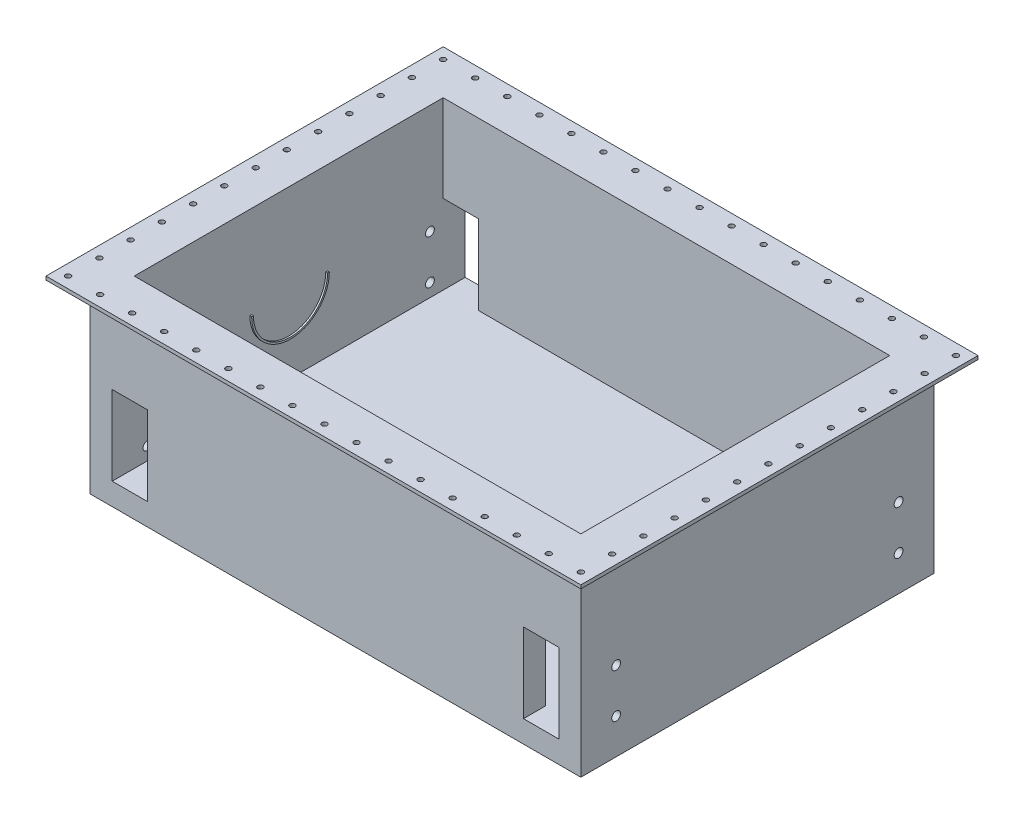
SolidWorks part; units mm, degrees
ref_plane "Front Plane" through (0, 0, 0) normal (0, 0, 1) x (1, 0, 0)
ref_plane "Top Plane" through (0, 0, 0) normal (0, 1, 0) x (1, 0, 0)
ref_plane "Right Plane" through (0, 0, 0) normal (1, 0, 0) x (0, 0, -1)
sketch "Sketch2" plane through (0, 0, 0) normal (0, 1, 0) x (1, 0, 0)
  line L0 (0, 437.5) -> (0, -437.5) construction
  line L1 (-632.5, 437.5) -> (632.5, 437.5)
  line L2 (-632.5, 437.5) -> (-632.5, -437.5)
  line L3 (-632.5, -437.5) -> (632.5, -437.5)
  line L4 (632.5, 437.5) -> (632.5, -437.5)
  line L5 (-632.5, 0) -> (632.5, 0) construction
  line L6 (-695, 48.7342) -> (-632.5, 48.7342) construction
  line L7 (-695, 500) -> (695, 500)
  line L8 (-695, 500) -> (-695, -500)
  line L9 (-695, -500) -> (695, -500)
  line L10 (695, 500) -> (695, -500)
  line L11 (632.5, 75.1796) -> (695, 75.1796) construction
  line L12 (-4.9015, 500) -> (-4.9015, 437.5) construction
  line L13 (-4.9015, -437.5) -> (-4.9015, -500) construction
  dimension "D1" = 62.5
  dimension "D2" = 1000
  dimension "D3" = 1390
extrude "Boss-Extrude1" add sketch "Sketch2" against normal blind 534.5
sketch "Sketch3" plane through (0, -534.5, 0) normal (0, -1, 0) x (1, 0, 0)
  line L0 (-695, 500) -> (-695, -500)
  line L3 (-695, 500) -> (695, 500)
  line L4 (695, -500) -> (695, 500)
  line L5 (-695, -500) -> (695, -500)
  line L6 (695, 500) -> (695, -500) construction
  line L7 (-695, 500) -> (695, 500) construction
  line L8 (-695, -500) -> (-695, 500) construction
  line L9 (695, -500) -> (-695, -500) construction
  point P0 (712.3016, -525.5001)
extrude "Boss-Extrude2" add sketch "Sketch3" against normal blind 62.5
sketch "Sketch4" plane through (695, 0, 0) normal (1, 0, 0) x (0, 0, -1)
  line L1 (0, 0) -> (0, -580.2055) construction
  line L2 (-105, -261) -> (-110, -261)
  line L3 (105, -261) -> (110, -261)
  arc A0 (-105, -261) -> (105, -261) centre (0, -261) ccw
  arc A1 (-110, -261) -> (110, -261) centre (0, -261) ccw
  dimension "D2" = 210
  dimension "D3" = 220
  dimension "D1" = 261
extrude "MMRTG Holder" add sketch "Sketch4" against normal blind 5 from offset 62.5 offset against normal yes
mirror "Mirror1" about plane through (0, 0, 0) normal (1, 0, 0) of "MMRTG Holder"
sketch "Sketch5" plane through (695, 0, 0) normal (1, 0, 0) x (0, 0, -1)
  line L0 (0, 70.8163) -> (0, -598.8061) construction
  line L1 (-500, -534.5) -> (500, -534.5) construction
  line L2 (-500, -534.5) -> (-500, 0) construction
  line L3 (-400, 39.1953) -> (-400, -618.3368) construction
  circle A0 centre (-400, -309.5) radius 12.5
  circle A1 centre (-400, -434.5) radius 12.5
  circle A2 centre (400, -434.5) radius 12.5
  circle A3 centre (400, -309.5) radius 12.5
  point P13 (-400, -434.5)
  point P14 (-400, -309.5)
  dimension "D4" = 25
  dimension "D1" = 125
  dimension "D2" = 100
  dimension "D3" = 100
extrude "Suspension Bolt Holes" cut sketch "Sketch5" against normal through all
sketch "Sketch6" plane through (0, 0, -500) normal (0, 0, -1) x (-1, 0, 0)
  line L0 (-695, -534.5) -> (-695, 0) construction
  line L1 (-632.5, -472) -> (-532.5, -472)
  line L2 (-632.5, -472) -> (-632.5, -247)
  line L3 (-632.5, -247) -> (-532.5, -247)
  line L4 (-532.5, -472) -> (-532.5, -247)
  line L5 (-695, -534.5) -> (695, -534.5) construction
  dimension "D1" = 62.5
  dimension "D2" = 62.5
  dimension "D3" = 100
  dimension "D4" = 225
extrude "Control Arm Cutout" cut sketch "Sketch6" against normal up to next
mirror "Mirror2" about plane through (0, 0, 0) normal (1, 0, 0) of "Control Arm Cutout"
mirror "Mirror3" about plane through (0, 0, 0) normal (0, 0, 1) of "Mirror2", "Control Arm Cutout"
sketch "Sketch7" plane through (0, 0, 0) normal (0, 1, 0) x (1, 0, 0)
  line L0 (695, 500) -> (-695, 500) construction
  line L1 (-757.5, 562.5) -> (757.5, 562.5)
  line L2 (-757.5, 562.5) -> (-757.5, -562.5)
  line L3 (-757.5, -562.5) -> (757.5, -562.5)
  line L4 (757.5, 562.5) -> (757.5, -562.5)
  line L5 (695, -500) -> (695, 500) construction
  line L7 (0, 562.5) -> (0, 500) construction
  line L8 (-632.5, 437.5) -> (632.5, 437.5)
  line L10 (0, -562.5) -> (0, -500) construction
  line L11 (-695, -500) -> (695, -500) construction
  line L12 (-632.5, 437.5) -> (-632.5, -437.5)
  line L13 (-632.5, -437.5) -> (632.5, -437.5)
  line L14 (632.5, 437.5) -> (632.5, -437.5)
  point P12 (0, 0)
  point P21 (0, 0)
  dimension "D1" = 62.5
  dimension "D2" = 62.5
  dimension "D3" = 62.5
extrude "AttachRoverFlange" add sketch "Sketch7" against normal blind 10
sketch "Sketch10" plane through (0, 0, 0) normal (0, 1, 0) x (1, 0, 0)
  line L0 (-726.25, 531.25) -> (-726.25, -475.2943) construction
  line L1 (-757.5, 562.5) -> (-757.5, -562.5) construction
  line L2 (757.5, 562.5) -> (-757.5, 562.5) construction
  line L3 (0, 0) -> (-1003.0581, 0) construction
  line L4 (-733.75, 0) -> (-718.75, 0)
  line L5 (0, 0) -> (0, 752.0536) construction
  line L6 (-726.25, 531.25) -> (0, 531.25) construction
  line L7 (0, 538.75) -> (0, 523.75)
  circle A0 centre (-726.25, 531.25) radius 7.5
  circle A1 centre (-726.25, 442.7083) radius 7.5
  circle A2 centre (-726.25, 354.1667) radius 7.5
  circle A3 centre (-726.25, 265.625) radius 7.5
  circle A4 centre (-635.4687, 531.25) radius 7.5
  circle A5 centre (-726.25, 177.0833) radius 7.5
  circle A6 centre (-726.25, 88.5417) radius 7.5
  circle A7 centre (-726.25, 0) radius 7.5
  circle A8 centre (-544.6875, 531.25) radius 7.5
  circle A9 centre (-453.9062, 531.25) radius 7.5
  circle A10 centre (-363.125, 531.25) radius 7.5
  circle A11 centre (-272.3437, 531.25) radius 7.5
  circle A12 centre (-181.5625, 531.25) radius 7.5
  circle A13 centre (0, 531.25) radius 7.5
  circle A14 centre (-90.7812, 531.25) radius 7.5
  circle A15 centre (90.7812, 531.25) radius 7.5
  circle A16 centre (181.5625, 531.25) radius 7.5
  circle A17 centre (272.3437, 531.25) radius 7.5
  circle A18 centre (363.125, 531.25) radius 7.5
  circle A19 centre (453.9062, 531.25) radius 7.5
  circle A20 centre (544.6875, 531.25) radius 7.5
  circle A21 centre (635.4687, 531.25) radius 7.5
  circle A22 centre (726.25, 531.25) radius 7.5
  circle A23 centre (726.25, 0) radius 7.5
  circle A24 centre (726.25, 88.5417) radius 7.5
  circle A25 centre (726.25, 177.0833) radius 7.5
  circle A26 centre (726.25, 265.625) radius 7.5
  circle A27 centre (726.25, 354.1667) radius 7.5
  circle A28 centre (726.25, 442.7083) radius 7.5
  circle A29 centre (726.25, -88.5417) radius 7.5
  circle A30 centre (726.25, -177.0833) radius 7.5
  circle A31 centre (726.25, -265.625) radius 7.5
  circle A32 centre (726.25, -354.1667) radius 7.5
  circle A33 centre (726.25, -442.7083) radius 7.5
  circle A34 centre (726.25, -531.25) radius 7.5
  circle A35 centre (635.4687, -531.25) radius 7.5
  circle A36 centre (544.6875, -531.25) radius 7.5
  circle A37 centre (453.9062, -531.25) radius 7.5
  circle A38 centre (363.125, -531.25) radius 7.5
  circle A39 centre (272.3437, -531.25) radius 7.5
  circle A40 centre (181.5625, -531.25) radius 7.5
  circle A41 centre (90.7812, -531.25) radius 7.5
  circle A42 centre (0, -531.25) radius 7.5
  circle A43 centre (-90.7812, -531.25) radius 7.5
  circle A44 centre (-181.5625, -531.25) radius 7.5
  circle A45 centre (-272.3437, -531.25) radius 7.5
  circle A46 centre (-363.125, -531.25) radius 7.5
  circle A47 centre (-453.9062, -531.25) radius 7.5
  circle A48 centre (-544.6875, -531.25) radius 7.5
  circle A49 centre (-635.4687, -531.25) radius 7.5
  circle A50 centre (-726.25, -531.25) radius 7.5
  circle A51 centre (-726.25, -354.1667) radius 7.5
  circle A52 centre (-726.25, -442.7083) radius 7.5
  circle A53 centre (-726.25, -265.625) radius 7.5
  circle A54 centre (-726.25, -177.0833) radius 7.5
  circle A55 centre (-726.25, -88.5417) radius 7.5
  dimension "D1" = 15
  dimension "D2" = 31.25
  dimension "D3" = 31.25
  dimension "D4" = 88.5417
  dimension "D5" = 88.5417
  dimension "D6" = 88.5417
  dimension "D7" = 88.5417
  dimension "D8" = 88.5417
  dimension "D9" = 90.7812
  dimension "D10" = 90.7812
  dimension "D11" = 90.7812
  dimension "D12" = 90.7812
  dimension "D13" = 90.7812
  dimension "D14" = 90.7812
  dimension "D15" = 90.7812
extrude "Attachment Holes" cut sketch "Sketch10" against normal up to next (10 mm away) contours L4 A7 | L4 A7 | A6 | A5 | A3 | A2 | A1 | A0 | A4 | A8 | A9 | A10 | A11 | A12 | A14 | L7 A13 | L7 A13 | A15 | A16 | A17 | A18 | A19 | A20 | A21 | A22 | A28 | A27 | A26 | A25 | A24 | A23 | A29 | A30 | A31 | A32 | A33 | A34 | A35 | A36 | A39 | A38 | A37 | A42 | A41 | A40 | A43 | A44 | A45 | A46 | A47 | A48 | A49 | A50 | A52 | A51 | A55 | A54 | A53 region at (-726.25, 0, -3.1831) region at (-726.25, 0, 3.1831) region at (3.1831, 0, -531.25) region at (-3.1831, 0, -531.25) region at (-726.25, 0, -531.25) region at (-726.25, 0, -442.7083) region at (-726.25, 0, -354.1667) region at (-726.25, 0, -265.625) region at (-635.4687, 0, -531.25) region at (-726.25, 0, -177.0833) region at (-726.25, 0, -88.5417) region at (-544.6875, 0, -531.25) region at (-453.9062, 0, -531.25) region at (-363.125, 0, -531.25) region at (-272.3437, 0, -531.25) region at (-181.5625, 0, -531.25) region at (-90.7812, 0, -531.25) region at (90.7812, 0, -531.25) region at (181.5625, 0, -531.25) region at (272.3437, 0, -531.25) region at (363.125, 0, -531.25) region at (453.9062, 0, -531.25) region at (544.6875, 0, -531.25) region at (635.4687, 0, -531.25) region at (726.25, 0, -531.25) region at (726.25, 0, 0) region at (726.25, 0, -88.5417) region at (726.25, 0, -177.0833) region at (726.25, 0, -265.625) region at (726.25, 0, -354.1667) region at (726.25, 0, -442.7083) region at (726.25, 0, 88.5417) region at (726.25, 0, 177.0833) region at (726.25, 0, 265.625) region at (726.25, 0, 354.1667) region at (726.25, 0, 442.7083) region at (726.25, 0, 531.25) region at (635.4687, 0, 531.25) region at (544.6875, 0, 531.25) region at (453.9062, 0, 531.25) region at (363.125, 0, 531.25) region at (272.3437, 0, 531.25) region at (181.5625, 0, 531.25) region at (90.7812, 0, 531.25) region at (0, 0, 531.25) region at (-90.7812, 0, 531.25) region at (-181.5625, 0, 531.25) region at (-272.3437, 0, 531.25) region at (-363.125, 0, 531.25) region at (-453.9062, 0, 531.25) region at (-544.6875, 0, 531.25) region at (-635.4687, 0, 531.25) region at (-726.25, 0, 531.25) region at (-726.25, 0, 354.1667) region at (-726.25, 0, 442.7083) region at (-726.25, 0, 265.625) region at (-726.25, 0, 177.0833) region at (-726.25, 0, 88.5417)
equation "\"D3@Sketch2\"=1140+(4*(62.5))"
equation "\"D1@Boss-Extrude1\"=422+62.5+50"
equation "\"D4@Sketch10\"=531.25/6"
equation "\"D5@Sketch10\"=531.25/6"
equation "\"D6@Sketch10\"=531.25/6"
equation "\"D7@Sketch10\"=531.25/6"
equation "\"D8@Sketch10\"=531.25/6"
equation "\"D9@Sketch10\"=726.25/8"
equation "\"D10@Sketch10\"=726.25/8"
equation "\"D11@Sketch10\"=726.25/8"
equation "\"D12@Sketch10\"=726.25/8"
equation "\"D13@Sketch10\"=726.25/8"
equation "\"D14@Sketch10\"=726.25/8"
equation "\"D15@Sketch10\"=726.25/8"
